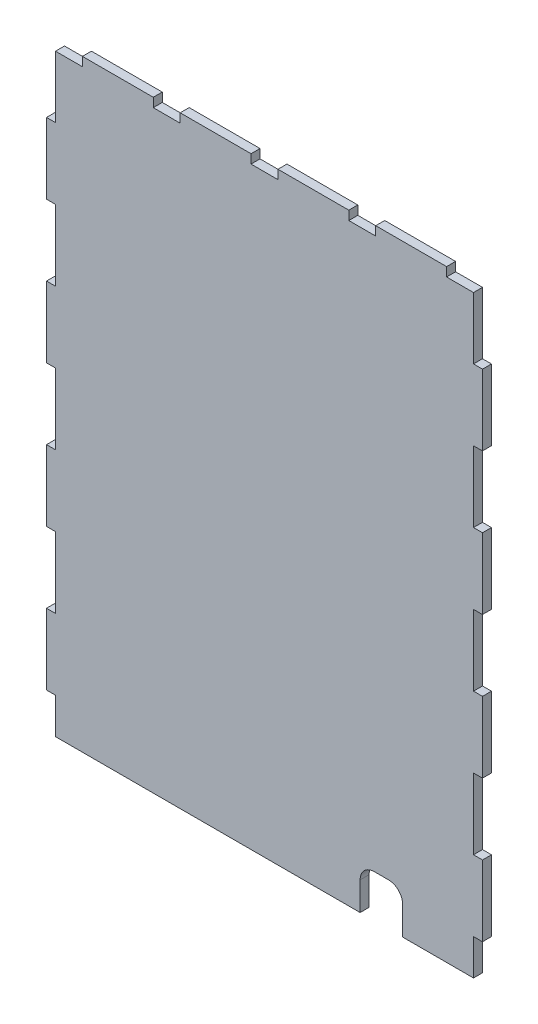
SolidWorks part; units mm, degrees
material "Beech"
ref_plane "Front Plane" through (0, 0, 0) normal (0, 0, 1) x (1, 0, 0)
ref_plane "Top Plane" through (0, 0, 0) normal (0, 1, 0) x (1, 0, 0)
ref_plane "Right Plane" through (0, 0, 0) normal (1, 0, 0) x (0, 0, -1)
sketch "Sketch2" plane through (0, 0, 0) normal (0, 0, 1) x (1, 0, 0)
  line L1 (0, 0) -> (19, 0)
  line L3 (0, -418.97) -> (295, -418.97)
  line L6 (19, 0) -> (19, 6.35)
  line L7 (19, 6.35) -> (69, 6.35)
  line L8 (69, 0) -> (69, 6.35)
  line L9 (88, 0) -> (88, 6.35)
  line L10 (88, 6.35) -> (138, 6.35)
  line L11 (138, 0) -> (138, 6.35)
  line L13 (157, 0) -> (157, 6.35)
  line L14 (157, 6.35) -> (207, 6.35)
  line L15 (207, 0) -> (207, 6.35)
  line L17 (226, 0) -> (226, 6.35)
  line L18 (226, 6.35) -> (276, 6.35)
  line L19 (276, 0) -> (276, 6.35)
  line L20 (69, 0) -> (88, 0)
  line L21 (138, 0) -> (157, 0)
  line L22 (207, 0) -> (226, 0)
  line L23 (276, 0) -> (295, 0)
  line L104 (0, 0) -> (0, -43.65)
  line L106 (0, -43.65) -> (-6.35, -43.65)
  line L108 (0, -93.65) -> (-6.35, -93.65)
  line L109 (-6.35, -43.65) -> (-6.35, -93.65)
  line L110 (0, -143.65) -> (-6.35, -143.65)
  line L111 (-6.35, -143.65) -> (-6.35, -193.65)
  line L112 (0, -193.65) -> (-6.35, -193.65)
  line L114 (0, -243.65) -> (-6.35, -243.65)
  line L115 (-6.35, -243.65) -> (-6.35, -293.65)
  line L116 (0, -293.65) -> (-6.35, -293.65)
  line L118 (0, -343.65) -> (-6.35, -343.65)
  line L119 (-6.35, -343.65) -> (-6.35, -393.65)
  line L120 (0, -393.65) -> (-6.35, -393.65)
  line L121 (0, -93.65) -> (0, -143.65)
  line L122 (0, -193.65) -> (0, -243.65)
  line L123 (0, -293.65) -> (0, -343.65)
  line L124 (0, -393.65) -> (0, -418.97)
  line L125 (295, 0) -> (295, -43.65)
  line L127 (295, -43.65) -> (301.35, -43.65)
  line L129 (295, -93.65) -> (301.35, -93.65)
  line L130 (301.35, -43.65) -> (301.35, -93.65)
  line L131 (295, -143.65) -> (301.35, -143.65)
  line L132 (301.35, -143.65) -> (301.35, -193.65)
  line L133 (295, -193.65) -> (301.35, -193.65)
  line L135 (295, -243.65) -> (301.35, -243.65)
  line L136 (301.35, -243.65) -> (301.35, -293.65)
  line L137 (295, -293.65) -> (301.35, -293.65)
  line L139 (295, -343.65) -> (301.35, -343.65)
  line L140 (301.35, -343.65) -> (301.35, -393.65)
  line L141 (295, -393.65) -> (301.35, -393.65)
  line L142 (295, -93.65) -> (295, -143.65)
  line L143 (295, -193.65) -> (295, -243.65)
  line L144 (295, -293.65) -> (295, -343.65)
  line L145 (295, -393.65) -> (295, -418.97)
  dimension "D1" = 295
  dimension "D2" = 418.97
  dimension "D3" = 6.35
  dimension "D4" = 50
  dimension "D5" = 6.35
  dimension "D7" = 50
  dimension "D8" = 43.65
  dimension "D9" = 6.35
  dimension "D10" = 50
  dimension "D11" = 43.65
  dimension "D6" = 4
extrude "Boss-Extrude1" add sketch "Sketch2" along normal blind 6.35
sketch "Sketch3" plane through (0, 0, 6.35) normal (0, 0, 1) x (1, 0, 0)
  line L1 (215, -418.97) -> (245, -418.97)
  line L2 (215, -418.97) -> (215, -388.97)
  line L3 (215, -388.97) -> (245, -388.97)
  line L4 (245, -418.97) -> (245, -388.97)
  line L5 (0, -418.97) -> (295, -418.97) construction
  line L7 (295, -418.97) -> (295, -393.65) construction
  dimension "D1" = 30
  dimension "D2" = 30
  dimension "D3" = 50
extrude "Cut-Extrude1" cut sketch "Sketch3" against normal through all
fillet "Fillet1" radius 10 2 edges at (245, -388.97, 3.175) (215, -388.97, 3.175)
